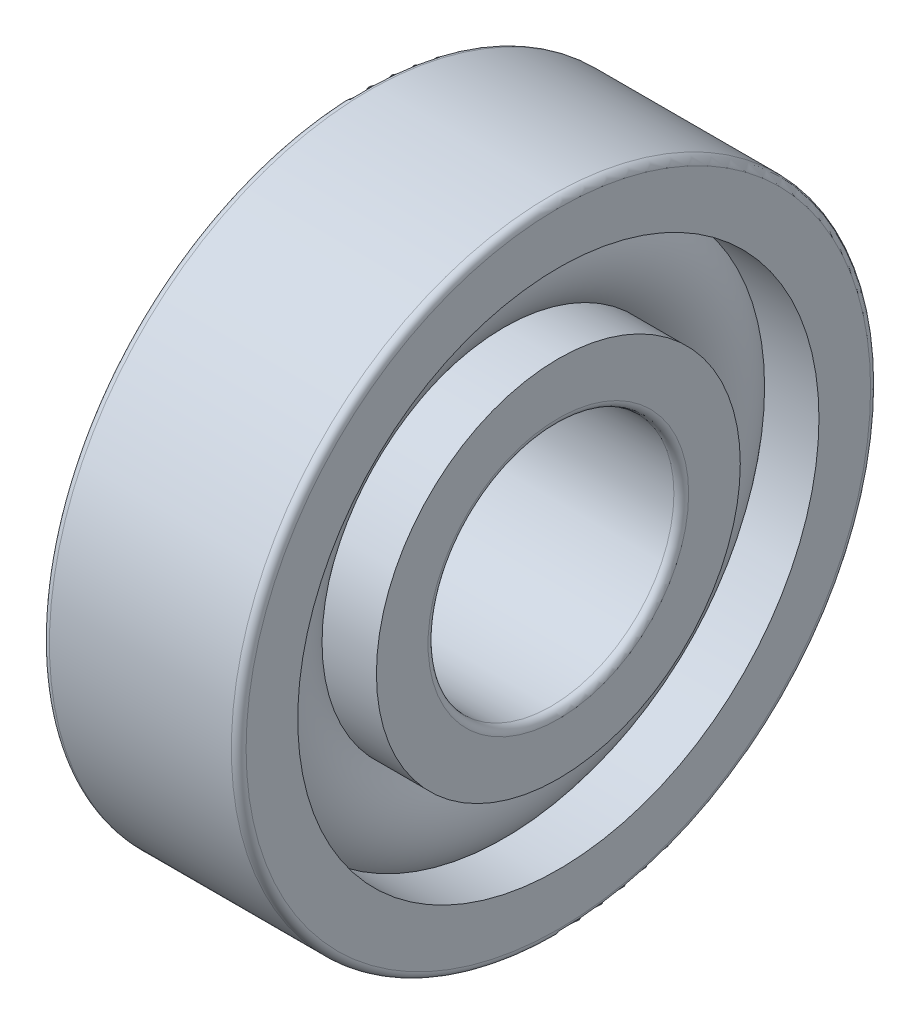
SolidWorks part; units mm, degrees
ref_plane "Plane1" through (0, 0, 0) normal (0, 0, 1) x (1, 0, 0)
ref_plane "Plane2" through (0, 0, 0) normal (0, 1, 0) x (1, 0, 0)
ref_plane "Plane3" through (0, 0, 0) normal (1, 0, 0) x (0, 0, -1)
sketch "Clipboard" plane through (0, 0, 0) normal (0, 0, 1) x (1, 0, 0)
  line L0 (-10, 0) -> (10, 0) construction
  line L1 (0, 0) -> (22.3471, -0.7804)
  line L2 (0, 0) -> (8.9945, 0.3141)
  line L3 (0, 0) -> (22.3471, -0.7804)
  line L4 (0, 0) -> (-22.3573, -0.3902)
  dimension "BallCLRad" = 9
sketch "CagSpiSke" plane through (0, 0, 0) normal (0, 0, 1) x (1, 0, 0)
  line L0 (0.24, 8.6) -> (0.24, 9.4)
  line L1 (0.24, 9.4) -> (-0.24, 9.4)
  line L2 (-0.24, 9.4) -> (-0.24, 8.6)
  line L3 (-0.24, 8.6) -> (0.24, 8.6)
  line L4 (-20.6375, 0) -> (20.6375, 0) construction
  line L5 (0, 0) -> (0, 23.7692) construction
  dimension "OD" = 18.8
  dimension "ID" = 17.2
revolve "CageSpine" add sketch "CagSpiSke" angle 0.001 about L4 reverse direction yes
ref_axis "Axis1" through (-50, 0, 0) along (1, 0, 0)
sketch "CagBalSke" plane through (0, 0, 0) normal (0, 0, 1) x (1, 0, 0)
  line L0 (-2.64, 9) -> (2.64, 9)
  line L1 (-1.905, 9) -> (1.905, 9) construction
  line L2 (-10, 0) -> (10, 0) construction
  line L3 (0, 0) -> (0, 24) construction
  arc A0 (2.64, 9) -> (-2.64, 9) centre (0, 9) cw
  dimension "BallCLRad" = 9
revolve "CageBall" [suppressed] add sketch "CagBalSke" angle 360 about L1 reverse direction yes
pattern_circular "CageBalls" [suppressed] count 2 every 180 about axis through (-50, 0, 0) along (1, 0, 0)
sketch "CagTrmODSke" plane through (0, 0, 0) normal (0, 0, 1) x (1, 0, 0)
  line L0 (2.641, 9.4) -> (2.641, 11.641)
  line L1 (2.641, 11.641) -> (-2.641, 11.641)
  line L2 (-2.641, 11.641) -> (-2.641, 9.4)
  line L3 (-2.641, 9.4) -> (2.641, 9.4)
  line L4 (-20.6375, 0) -> (20.6375, 0) construction
  line L5 (0, 0) -> (0, 25) construction
  dimension "Width" = 5.282
  dimension "ID" = 18.8
  dimension "OD" = 23.282
revolve "CageTrimOD" [suppressed] cut sketch "CagTrmODSke" angle 360 about L4 reverse direction yes
sketch "CagTrmIDSke" plane through (0, 0, 0) normal (0, 0, 1) x (1, 0, 0)
  line L0 (2.641, 6.361) -> (2.641, 8.6)
  line L1 (2.641, 8.6) -> (-2.641, 8.6)
  line L2 (-2.641, 8.6) -> (-2.641, 6.361)
  line L3 (-2.641, 6.361) -> (2.641, 6.361)
  line L4 (-20.6375, 0) -> (20.6375, 0) construction
  line L5 (0, 0) -> (0, 25) construction
  dimension "Width" = 5.282
  dimension "ID" = 12.722
  dimension "OD" = 17.2
revolve "CageTrimID" [suppressed] cut sketch "CagTrmIDSke" angle 360 about L4 reverse direction yes
sketch "BalSimSke" plane through (0, 0, 0) normal (0, 0, 1) x (1, 0, 0)
  line L0 (-10, 0) -> (10, 0) construction
  line L1 (-10, 9) -> (10, 9) construction
  line L2 (0, 0) -> (0, 23) construction
  circle A0 centre (0, 9) radius 2.4
  dimension "BallCLRad" = 9
  dimension "Ball_diameter" = 4.8
revolve "BallsSimplified" add sketch "BalSimSke" angle 360 about L0
sketch "BalDetSke" plane through (0, 0, 0) normal (0, 0, 1) x (1, 0, 0)
  line L0 (-2.4, 9) -> (2.4, 9)
  line L1 (-1.905, 9) -> (1.905, 9) construction
  line L2 (0, 0) -> (0, 25) construction
  arc A0 (2.4, 9) -> (-2.4, 9) centre (0, 9) cw
  dimension "BallCLRad" = 9
  dimension "Ball_diameter" = 4.8
revolve "BallDetailed" [suppressed] add sketch "BalDetSke" angle 360 about L1 reverse direction yes
sketch "InnRacSke" plane through (0, 0, 0) normal (0, 0, 1) x (1, 0, 0)
  line L0 (-1.7552, 7.4) -> (-4, 7.4)
  line L1 (-4, 7.4) -> (-4, 5.3)
  line L2 (-3.7, 5) -> (3.7, 5)
  line L3 (4, 5.3) -> (4, 7.4)
  line L4 (4, 7.4) -> (1.7552, 7.4)
  line L5 (-20.6375, 0) -> (20.6375, 0) construction
  line L6 (0, 0) -> (0, 30) construction
  arc A0 (-4, 5.3) -> (-3.7, 5) centre (-3.7, 5.3) ccw
  arc A1 (3.7, 5) -> (4, 5.3) centre (3.7, 5.3) ccw
  arc A2 (1.7552, 7.4) -> (-1.7552, 7.4) centre (0, 9) cw
  dimension "BallCLRad" = 9
  dimension "Fillet_radius" = 0.3
  dimension "Ball_diameter" = 4.75
  dimension "ID" = 10
  dimension "OD" = 14.8
  dimension "Width" = 8
revolve "InnerRace" add sketch "InnRacSke" angle 360 about L5 reverse direction yes
sketch "OutRacSke" plane through (0, 0, 0) normal (0, 0, 1) x (1, 0, 0)
  line L0 (-1.7552, 10.6) -> (-4, 10.6)
  line L1 (-4, 10.6) -> (-4, 12.7)
  line L2 (-3.7, 13) -> (3.7, 13)
  line L3 (4, 12.7) -> (4, 10.6)
  line L4 (4, 10.6) -> (1.7552, 10.6)
  line L5 (-20.6375, 0) -> (20.6375, 0) construction
  line L6 (0, 0) -> (0, 30) construction
  arc A0 (-4, 12.7) -> (-3.7, 13) centre (-3.7, 12.7) cw
  arc A1 (3.7, 13) -> (4, 12.7) centre (3.7, 12.7) cw
  arc A2 (1.7552, 10.6) -> (-1.7552, 10.6) centre (0, 9) ccw
  dimension "BallCLRad" = 9
  dimension "Fillet_radius" = 0.3
  dimension "Ball_diameter" = 4.75
  dimension "Width" = 8
revolve "OuterRace" add sketch "OutRacSke" angle 360 about L5 reverse direction yes
pattern_circular "BallsDetailed" [suppressed] count 2 every 180 about axis through (-50, 0, 0) along (1, 0, 0)
equation "\"BallCLRad@Clipboard\" = ( \"OD@OutRacSke\" + \"ID@InnRacSke\" ) / 4"
equation "\"BallCLRad@BalSimSke\" = \"BallCLRad@Clipboard\""
equation "\"BallCLRad@BalDetSke\" = \"BallCLRad@Clipboard\""
equation "\"BallCLRad@InnRacSke\" = \"BallCLRad@Clipboard\""
equation "\"BallCLRad@OutRacSke\" = \"BallCLRad@Clipboard\""
equation "\"Ball_diameter@InnRacSke\" = \"Ball_diameter@BalDetSke\" - 0.05"
equation "\"Ball_diameter@OutRacSke\" = \"Ball_diameter@BalDetSke\" - 0.05"
equation "\"Ball_diameter@BalSimSke\" = \"Ball_diameter@BalDetSke\""
equation "\"Width@OutRacSke\" = \"Width@InnRacSke\""
equation "\"Fillet_radius@OutRacSke\" = \"Fillet_radius@InnRacSke\""
equation "\"Max_count@Clipboard\" = int( 3.14159265 / atn(( \"Ball_diameter@BalDetSke\" / 2) / sqr( \"BallCLRad@Clipboard\"  *  \"BallCLRad@Clipboard\" - ( \"Ball_diameter@BalDetSke\" / 2) *  ( \"Ball_diameter@BalDetSke\" / 2))))"
equation "\"Max_count@Clipboard\" = ((sgn( \"Max_count@Clipboard\" - \"Count@Clipboard\" )-1)*( \"Max_count@Clipboard\" - \"Count@Clipboard\" ))/-2+ \"Count@Clipboard\""
equation "\"Count@BallsDetailed\" = int( \"Show_count@Clipboard\" ) "
equation "\"Count@BallsDetailed\" = ((sgn( \"Count@BallsDetailed\" - \"Max_count@Clipboard\" )-1)*( \"Count@BallsDetailed\" - \"Max_count@Clipboard\" ))/-2+ \"Max_count@Clipboard\""
equation "\"Count@BallsDetailed\" = ((sgn( \"Count@BallsDetailed\" - \"Min_count@Clipboard\" )+1)*( \"Count@BallsDetailed\" - \"Min_count@Clipboard\"))/2 +\"Min_count@Clipboard\""
equation "\"Angle@BallsDetailed\" = 360.0 / \"Max_count@Clipboard\""
equation "\"BallCLRad@CagBalSke\" = \"BallCLRad@Clipboard\""
equation "\"Count@CageBalls\" = \"Count@BallsDetailed\""
equation "\"Angle@CageBalls\" = \"Angle@BallsDetailed\""
equation "\"Angle@CageSpine\" =  \"Angle@CageBalls\" * ( \"Count@CageBalls\" -1 + int( \"Count@CageBalls\" / \"Max_count@Clipboard\" ) )  + 0.001 -  int( \"Count@CageBalls\" / \"Max_count@Clipboard\" ) * 0.001"
equation "\"Angle@CageSpine\" =  \"Angle@CageSpine\" * int( \"Min_count@Clipboard\" / 2) + int(1 / \"Min_count@Clipboard\")  * 0.001"
equation "\"CageWallOD@CagBalSke\" =  \"Ball_diameter@BalDetSke\" * 1.1"
equation "\"Thickness@CagSpiSke\" =  \"Ball_diameter@BalDetSke\" * 0.1"
equation "\"OD@CagTrmODSke\" = \"BallCLRad@Clipboard\" * 2 + \"CageWallOD@CagBalSke\" + 0.002"
equation "\"ID@CagTrmODSke\" = \"BallCLRad@Clipboard\" * 2 + \"Ball_diameter@BalDetSke\" / 6"
equation "\"OD@CagTrmIDSke\" = \"BallCLRad@Clipboard\" * 2 - \"Ball_diameter@BalDetSke\" / 6"
equation "\"ID@CagTrmIDSke\" = \"BallCLRad@Clipboard\" * 2 - \"CageWallOD@CagBalSke\" + 0.002"
equation "\"OD@CagSpiSke\" = \"ID@CagTrmODSke\""
equation "\"ID@CagSpiSke\" = \"OD@CagTrmIDSke\""
equation "\"Width@CagTrmODSke\" = \"CageWallOD@CagBalSke\" + 0.002"
equation "\"Width@CagTrmIDSke\" = \"CageWallOD@CagBalSke\" + 0.002"
